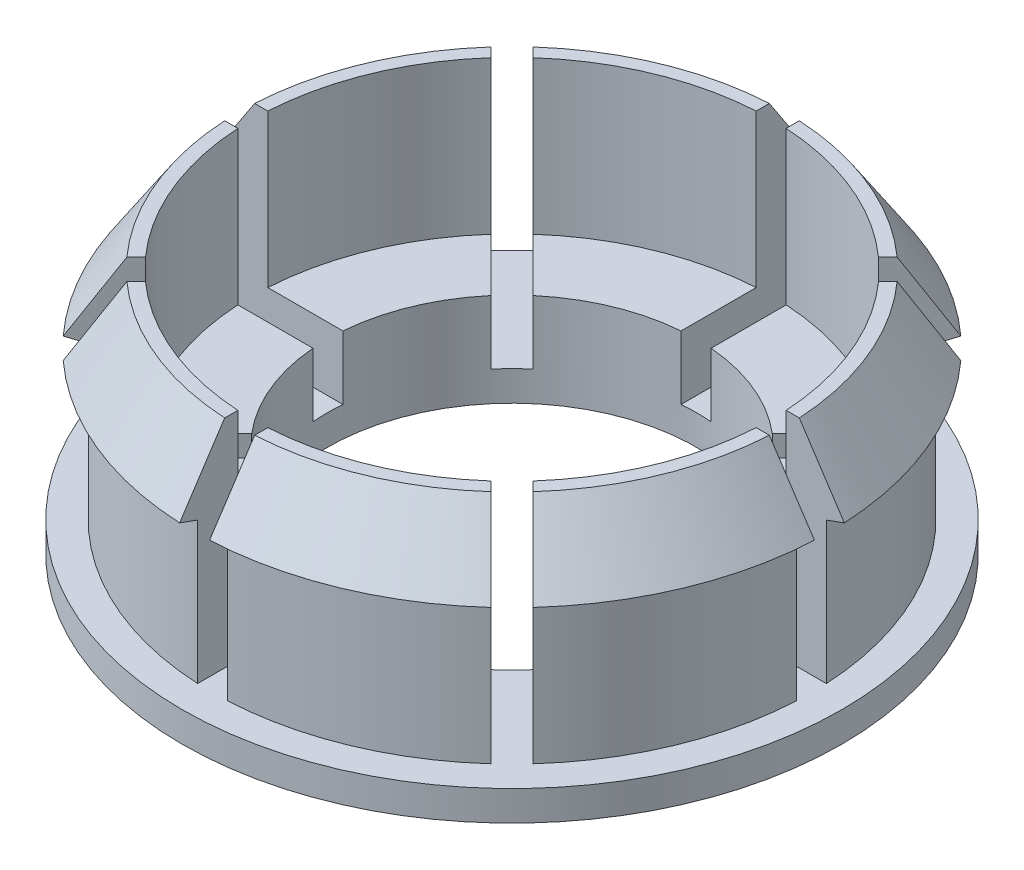
SolidWorks part; units mm, degrees
ref_plane "Front Plane" through (0, 0, 0) normal (0, 0, 1) x (1, 0, 0)
ref_plane "Top Plane" through (0, 0, 0) normal (0, 1, 0) x (1, 0, 0)
ref_plane "Right Plane" through (0, 0, 0) normal (1, 0, 0) x (0, 0, -1)
sketch "Sketch5" plane through (0, 0, 0) normal (0, 0, 1) x (1, 0, 0)
  line L0 (-11, -3.2385) -> (-11, 3.2385)
  line L1 (11, 3.2385) -> (-11, 3.2385) construction
  line L2 (11, 3.2385) -> (11, -3.2385) construction
  line L3 (11, -3.2385) -> (-11, -3.2385) construction
  line L4 (-11, 3.2385) -> (-11, -3.2385) construction
  line L5 (11, 3.2385) -> (-11, -3.2385) construction
  line L6 (11, -3.2385) -> (-11, 3.2385) construction
  line L7 (-11, 3.2385) -> (-11.557, 3.2385)
  line L8 (-11.557, 3.2385) -> (-13.462, 0.3408)
  line L9 (-13.462, 0.3408) -> (-12.7, 0.0635)
  line L10 (-12.7, 0.0635) -> (-12.7, -5.9365)
  line L11 (-12.7, -5.9365) -> (-13.97, -5.9365)
  line L12 (-13.97, -5.9365) -> (-13.97, -7.2065)
  line L13 (-13.97, -7.2065) -> (-7.825, -7.2065)
  line L14 (-7.825, -7.2065) -> (-7.825, -3.2385)
  line L15 (-7.825, -3.2385) -> (-11, -3.2385)
  line L16 (0, 0.0635) -> (0, -8.827) construction
  line L17 (7.825, -7.2065) -> (-7.825, -7.2065) construction
  line L18 (7.825, -7.2065) -> (7.825, -3.2385) construction
  line L19 (7.825, -3.2385) -> (-7.825, -3.2385) construction
  line L20 (-7.825, -7.2065) -> (-7.825, -3.2385) construction
  line L21 (7.825, -7.2065) -> (-7.825, -3.2385) construction
  line L22 (7.825, -3.2385) -> (-7.825, -7.2065) construction
  line L23 (12.7, -5.9365) -> (-12.7, -5.9365) construction
  line L24 (12.7, -5.9365) -> (12.7, 0.0635) construction
  line L25 (12.7, 0.0635) -> (-12.7, 0.0635) construction
  line L26 (-12.7, -5.9365) -> (-12.7, 0.0635) construction
  line L27 (12.7, -5.9365) -> (-12.7, 0.0635) construction
  line L28 (12.7, 0.0635) -> (-12.7, -5.9365) construction
  line L30 (11, 3.7615) -> (-11, 3.7615) construction
  line L31 (11, 3.7615) -> (11, -3.2385) construction
  line L32 (11, -3.2385) -> (-11, -3.2385) construction
  line L33 (-11, 3.7615) -> (-11, -3.2385) construction
  line L34 (11, 3.7615) -> (-11, -3.2385) construction
  line L35 (11, -3.2385) -> (-11, 3.7615) construction
  point P0 (0, 0)
  point P7 (0, -5.2225)
  point P15 (0, 0.2615)
  point P19 (0, -2.9365)
  point P20 (0, 0)
  dimension "D2" = 22
  dimension "D3" = 3.175
  dimension "D4" = 6
  dimension "D5" = 3.175
  dimension "D6" = 25.4
  dimension "D7" = 0.762
  dimension "D8" = 1.905
  dimension "D9" = 1.27
  dimension "D10" = 1.27
  dimension "D11" = 70
  dimension "D12" = 3.302
  dimension "D13" = 7
revolve "Revolve1" add sketch "Sketch5" angle 360 about L16
sketch "Sketch6" plane through (0, 3.2385, 0) normal (0, 1, 0) x (1, 0, 0)
  line L1 (0.635, 0) -> (-0.635, 0)
  line L2 (0.635, 0) -> (0.635, 13.462)
  line L3 (0.635, 13.462) -> (-0.635, 13.462)
  line L4 (-0.635, 0) -> (-0.635, 13.462)
  line L5 (0.635, 0) -> (-0.635, 13.462) construction
  line L6 (0.635, 13.462) -> (-0.635, 0) construction
  circle A0 centre (0, 0) radius 13.462 construction
  point P0 (0, 6.731)
  dimension "D1" = 1.27
extrude "Cut-Extrude3" cut sketch "Sketch6" against normal up to surface (9.175 mm away) and the other way through all up to face at (0, -5.9365, 13.97)
ref_axis "Axis1" through (0, 4.0728, 0) along (0, -1, 0)
pattern_circular "CirPattern1" count 8 over 360 about axis through (0, 4.0728, 0) along (0, -1, 0) of "Cut-Extrude3"
